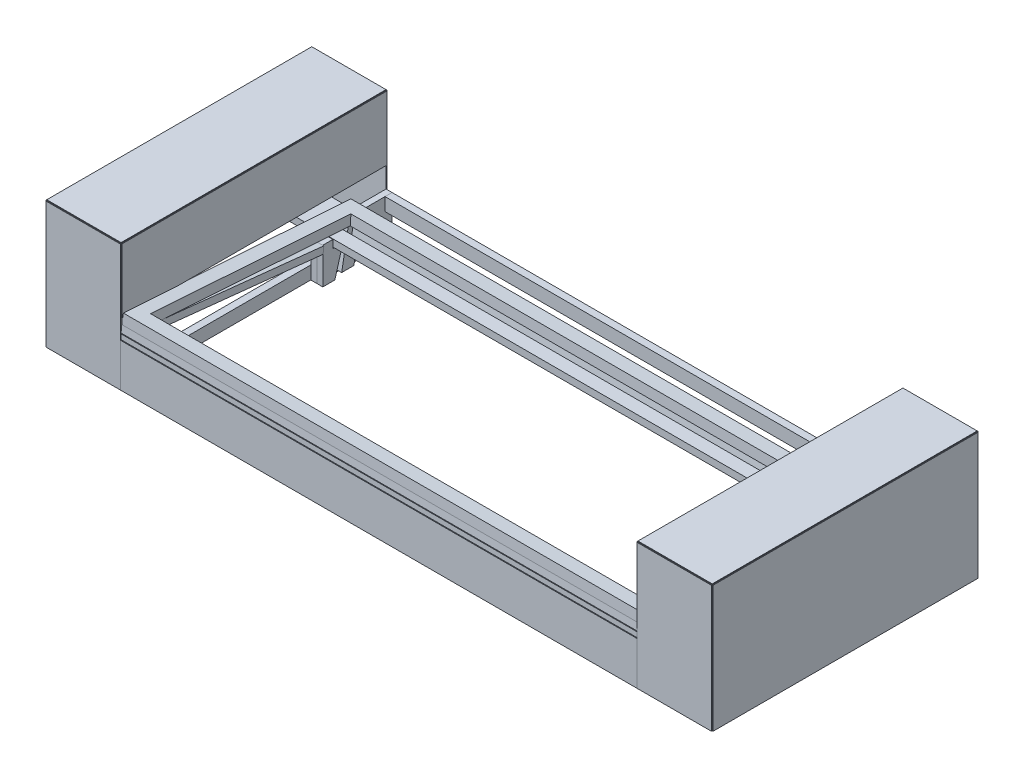
SolidWorks part; units mm, degrees
material "Balsa"
ref_plane "Front Plane" through (0, 0, 0) normal (0, 0, 1) x (1, 0, 0)
ref_plane "Top Plane" through (0, 0, 0) normal (0, 1, 0) x (1, 0, 0)
ref_plane "Right Plane" through (0, 0, 0) normal (1, 0, 0) x (0, 0, -1)
sketch "Sketch1" plane through (0, 0, 0) normal (0, 0, 1) x (1, 0, 0)
  line L0 (0, 0) -> (0, 288750.7845) construction
  line L1 (-817.5625, 0) -> (-1052.5125, 0) construction
  line L2 (-817.5625, 0) -> (-817.5625, 400.05) construction
  line L3 (-817.5625, 400.05) -> (-1052.5125, 400.05) construction
  line L4 (-1052.5125, 0) -> (-1052.5125, 400.05) construction
  line L5 (-1030.2875, 358.775) -> (-1030.2875, 219.075) construction
  line L6 (-1052.5125, 400.05) -> (-1030.2875, 400.05)
  line L7 (-1052.5125, 400.05) -> (-1052.5125, 358.775)
  line L8 (-1052.5125, 358.775) -> (-1030.2875, 358.775)
  line L9 (-1030.2875, 400.05) -> (-1030.2875, 358.775)
  line L10 (-955.675, 400.05) -> (-914.4, 400.05)
  line L11 (-955.675, 400.05) -> (-955.675, 377.825)
  line L12 (-955.675, 377.825) -> (-914.4, 377.825)
  line L13 (-914.4, 400.05) -> (-914.4, 377.825)
  line L14 (-817.5625, 400.05) -> (-839.7875, 400.05)
  line L15 (-817.5625, 400.05) -> (-817.5625, 358.775)
  line L16 (-817.5625, 358.775) -> (-839.7875, 358.775)
  line L17 (-839.7875, 400.05) -> (-839.7875, 358.775)
  line L18 (-1052.5125, 196.85) -> (-1030.2875, 196.85)
  line L19 (-1052.5125, 196.85) -> (-1052.5125, 219.075)
  line L20 (-1052.5125, 219.075) -> (-1030.2875, 219.075)
  line L21 (-1030.2875, 196.85) -> (-1030.2875, 219.075)
  line L22 (-817.5625, 196.85) -> (-839.7875, 196.85)
  line L23 (-817.5625, 196.85) -> (-817.5625, 219.075)
  line L24 (-817.5625, 219.075) -> (-839.7875, 219.075)
  line L25 (-839.7875, 196.85) -> (-839.7875, 219.075)
  line L26 (-1052.5125, 0) -> (-1030.2875, 0)
  line L27 (-1052.5125, 0) -> (-1052.5125, 41.275)
  line L28 (-1052.5125, 41.275) -> (-1030.2875, 41.275)
  line L29 (-1030.2875, 0) -> (-1030.2875, 41.275)
  line L30 (-817.5625, 0) -> (-839.7875, 0)
  line L31 (-817.5625, 0) -> (-817.5625, 41.275)
  line L32 (-817.5625, 41.275) -> (-839.7875, 41.275)
  line L33 (-839.7875, 0) -> (-839.7875, 41.275)
  line L34 (-1030.2875, 196.85) -> (-1030.2875, 41.275) construction
  line L35 (-839.7875, 41.275) -> (-839.7875, 196.85) construction
  line L36 (-839.7875, 219.075) -> (-839.7875, 358.775) construction
  line L37 (-1052.5125, 0) -> (-1052.5125, 400.05)
  line L38 (-839.7875, 0) -> (-1030.2875, 0)
  line L39 (-839.7875, 0) -> (-839.7875, 22.225)
  line L40 (-839.7875, 22.225) -> (-1030.2875, 22.225)
  line L41 (-1030.2875, 0) -> (-1030.2875, 22.225)
  line L42 (-817.5625, 400.05) -> (-1052.5125, 400.05)
  line L43 (-817.5625, 400.05) -> (-817.5625, 196.85)
  point P34 (-935.0375, 400.05)
  dimension "D1" = 22.225
  dimension "D2" = 41.275
  dimension "D3" = 190.5
  dimension "D4" = 400.05
  dimension "D5" = 196.85
  dimension "D6" = 1679.575
  dimension "D7" = 22.225
extrude "Boss-Extrude1" add sketch "Sketch1" along normal blind 838.2 contours L9 L6 L7 L8 | L13 L10 L11 L12 | L14 L17 L16 L15 | L25 L22 L23 L24 | L33 L30 L31 L32 | L26 L29 L28 L27 | L18 L21 L20 L19 region at (-828.675, 207.9625, 0) region at (-828.675, 379.4125, 0) region at (-935.0375, 388.9375, 0) region at (-1041.4, 20.6375, 0) region at (-1041.4, 207.9625, 0) region at (-1041.4, 379.4125, 0) region at (-828.675, 20.6375, 0)
extrude "Extrude-Thin1" add sketch "Sketch1<3>" along normal up to surface (838.2 mm away) separate body thin contours L42 up to face at (-1041.4, 379.4125, 838.2) thin type one direction wall 2.54
sketch "Sketch1<3>" plane through (0, 0, 0) normal (0, 0, 1) x (1, 0, 0) same geometry as "Sketch1"
extrude "Extrude-Thin2" add sketch "Sketch1<4>" along normal up to surface (838.2 mm away) separate body thin contours L37 up to face at (-1041.4, 379.4125, 838.2) thin type one direction reverse wall 2.54
sketch "Sketch1<4>" plane through (0, 0, 0) normal (0, 0, 1) x (1, 0, 0) same geometry as "Sketch1"
extrude "Extrude-Thin3" add sketch "Sketch1<5>" along normal blind 838.2 separate body thin contours L43 thin type one direction reverse wall 2.54
sketch "Sketch1<5>" plane through (0, 0, 0) normal (0, 0, 1) x (1, 0, 0) same geometry as "Sketch1"
sketch "Sketch2" plane through (-817.5625, 0, 0) normal (-1, 0, 0) x (0, 0, 1)
  line L0 (0, 219.075) -> (139.7, 219.075)
  line L1 (838.2, 219.075) -> (0, 219.075) construction
  line L2 (139.7, 219.075) -> (95.25, 358.775)
  line L3 (838.2, 358.775) -> (0, 358.775) construction
  line L4 (95.25, 358.775) -> (0, 358.775)
  line L5 (0, 358.775) -> (0, 219.075)
  dimension "D1" = 95.25
  dimension "D2" = 139.7
extrude "Boss-Extrude2" add sketch "Sketch2" along normal up to surface (22.225 mm away) separate body up to face at (-839.7875, 207.9625, 419.1)
sketch "Sketch3" plane through (0, 400.05, 0) normal (0, -1, 0) x (1, 0, 0)
  line L0 (-839.7875, 838.2) -> (-839.7875, 0) construction
  line L1 (-839.7875, 241.3) -> (-914.4, 241.3)
  line L2 (-839.7875, 241.3) -> (-839.7875, 282.575)
  line L3 (-839.7875, 282.575) -> (-914.4, 282.575)
  line L4 (-914.4, 241.3) -> (-914.4, 282.575)
  line L5 (-914.4, 838.2) -> (-914.4, 0) construction
  line L6 (-955.675, 838.2) -> (-955.675, 0) construction
  line L7 (-955.675, 241.3) -> (-1030.2875, 241.3)
  line L8 (-955.675, 241.3) -> (-955.675, 282.575)
  line L9 (-955.675, 282.575) -> (-1030.2875, 282.575)
  line L10 (-1030.2875, 241.3) -> (-1030.2875, 282.575)
  line L11 (-817.5625, 0) -> (-1052.5125, 0) construction
  line L12 (-839.7875, 584.2) -> (-914.4, 584.2)
  line L13 (-839.7875, 584.2) -> (-839.7875, 625.475)
  line L14 (-839.7875, 625.475) -> (-914.4, 625.475)
  line L15 (-914.4, 584.2) -> (-914.4, 625.475)
  line L16 (-955.675, 584.2) -> (-1030.2875, 584.2)
  line L17 (-955.675, 584.2) -> (-955.675, 625.475)
  line L18 (-955.675, 625.475) -> (-1030.2875, 625.475)
  line L19 (-1030.2875, 584.2) -> (-1030.2875, 625.475)
  line L20 (-1030.2875, 838.2) -> (-1030.2875, 0) construction
  point P24 (-1030.2875, 263.525)
  point P27 (-1030.2875, 584.2)
  dimension "D1" = 241.3
  dimension "D2" = 584.2
  dimension "D3" = 41.275
extrude "Boss-Extrude3" add sketch "Sketch3" along normal up to surface (22.225 mm away) separate body up to face at (-935.0375, 377.825, 419.1)
sketch "Sketch4" plane through (0, 0, 0) normal (0, -1, 0) x (1, 0, 0)
  line L0 (-839.7875, 838.2) -> (-839.7875, 0) construction
  line L1 (-1030.2875, 838.2) -> (-839.7875, 838.2)
  line L2 (-1030.2875, 838.2) -> (-1030.2875, 727.075)
  line L3 (-1030.2875, 727.075) -> (-839.7875, 727.075)
  line L4 (-839.7875, 838.2) -> (-839.7875, 727.075)
  line L5 (-1030.2875, 838.2) -> (-1030.2875, 0) construction
  line L6 (-839.7875, 0) -> (-1030.2875, 0)
  line L7 (-839.7875, 0) -> (-839.7875, 111.125)
  line L8 (-839.7875, 111.125) -> (-1030.2875, 111.125)
  line L9 (-1030.2875, 0) -> (-1030.2875, 111.125)
  line L10 (-817.5625, 838.2) -> (-1052.5125, 838.2)
  line L11 (-817.5625, 0) -> (-1052.5125, 0)
  line M3 (-1030.2875, 0) -> (-1030.2875, 838.2)
  dimension "D1" = 111.125
extrude "Boss-Extrude4" add sketch "Sketch4" against normal blind 22.225 separate body contours L7 L8 L6 M3 | L4 L1 L3 M3 region at (-935.0375, 0, 55.5625) region at (-935.0375, 0, 782.6375)
extrude "Extrude-Thin4" add sketch "Sketch4<3>" against normal up to surface (400.05 mm away) separate body thin contours L10 up to face at (-935.0375, 400.05, 419.1) thin type one direction wall 2.54
sketch "Sketch4<3>" plane through (0, 0, 0) normal (0, -1, 0) x (1, 0, 0) same geometry as "Sketch4"
extrude "Extrude-Thin5" add sketch "Sketch4<4>" against normal up to surface (400.05 mm away) separate body thin contours L11 up to face at (-935.0375, 400.05, 419.1) thin type one direction reverse wall 2.54
sketch "Sketch4<4>" plane through (0, 0, 0) normal (0, -1, 0) x (1, 0, 0) same geometry as "Sketch4"
mirror "Mirror Arm Geo" about plane through (0, 0, 0) normal (1, 0, 0) of bodies 115 134 103 107 114 104 137 108 135 109 113 111 105 101 133 102 106 110 112
sketch "Sketch5" plane through (-817.5625, 0, 0) normal (1, 0, 0) x (0, 0, -1)
  line L0 (-79.375, 126.2347) -> (-86.6927, 85.6136)
  line L1 (0, 0) -> (-238.125, 0)
  line L2 (0, 0) -> (0, 130.175)
  line L3 (0, 130.175) -> (-238.125, 130.175)
  line L4 (-238.125, 0) -> (-238.125, 130.175)
  line L5 (0, 22.225) -> (-41.275, 22.225)
  line L6 (0, 22.225) -> (0, 0)
  line L7 (0, 0) -> (-41.275, 0)
  line L8 (-41.275, 22.225) -> (-41.275, 0)
  line L9 (0, 130.175) -> (-22.225, 130.175)
  line L10 (0, 130.175) -> (0, 88.9)
  line L11 (0, 88.9) -> (-22.225, 88.9)
  line L12 (-22.225, 130.175) -> (-22.225, 88.9)
  line L13 (-204.8172, 92.075) -> (-163.5422, 92.075)
  line L14 (-204.8172, 92.075) -> (-204.8172, 114.3)
  line L15 (-204.8172, 114.3) -> (-163.5422, 114.3)
  line L16 (-163.5422, 92.075) -> (-163.5422, 114.3)
  line L17 (-79.375, 126.2347) -> (-101.2479, 130.175)
  line L18 (-86.6927, 85.6136) -> (-108.5656, 89.5539)
  line L19 (-101.2479, 130.175) -> (-108.5656, 89.5539)
  line L20 (-139.7, 9.525) -> (-178.4133, 9.525)
  line L21 (-178.4133, 9.525) -> (-156.6787, 130.175)
  line L22 (-156.6787, 130.175) -> (-119.1823, 123.4202)
  line L23 (-119.1823, 123.4202) -> (-139.7, 9.525)
  line L24 (-119.1823, 123.4202) -> (-126.5, 82.799)
  line L25 (-126.5, 82.799) -> (-148.3729, 86.7394)
  line L26 (-148.3729, 86.7394) -> (-141.0552, 127.3605)
  line L27 (-141.0552, 127.3605) -> (-119.1823, 123.4202)
  line L28 (-200.025, 0) -> (-174.625, 88.9)
  line L29 (-174.625, 88.9) -> (-206.375, 88.9)
  line L30 (-206.375, 88.9) -> (-206.375, 114.3)
  line L31 (-206.375, 114.3) -> (-238.125, 114.3)
  line L32 (-838.2, 0) -> (-838.2, 136.525)
  line L33 (-838.2, 0) -> (-815.975, 0)
  line L34 (-838.2, 0) -> (-838.2, 41.275)
  line L35 (-838.2, 41.275) -> (-815.975, 41.275)
  line L36 (-815.975, 0) -> (-815.975, 41.275)
  line L37 (-838.2, 400.05) -> (-838.2, 196.85) construction
  line L38 (-838.2, 196.85) -> (-838.2, 219.075) construction
  line L39 (-838.2, 154.7249) -> (-240.4372, 92.1956)
  line L40 (-815.975, 111.125) -> (-838.2, 111.125)
  line L41 (-815.975, 111.125) -> (-815.975, 152.4)
  line L42 (-815.975, 152.4) -> (-838.2, 152.4)
  line L43 (-838.2, 111.125) -> (-838.2, 152.4)
  line L44 (-838.2, 154.7249) -> (-835.8878, 176.8292)
  line L45 (-240.4372, 92.1956) -> (-238.125, 114.3)
  line L46 (-835.8878, 176.8292) -> (-238.125, 114.3)
  line L47 (-838.2, 400.05) -> (-838.2, 0) construction
  line L48 (-838.2, 0) -> (0, 0) construction
  line L49 (-815.975, 12.7) -> (-793.75, 12.7)
  line L50 (-815.975, 12.7) -> (-815.975, 150.0751)
  line L51 (-815.975, 150.0751) -> (-793.75, 150.0751)
  line L52 (-793.75, 12.7) -> (-793.75, 150.0751)
  line L53 (-835.8878, 176.8292) -> (-113.3916, 127.2017)
  line L54 (-835.8878, 176.8292) -> (-833.7069, 208.5792)
  line L55 (-113.3916, 127.2017) -> (-111.2108, 158.9517)
  line L56 (-833.7069, 208.5792) -> (-111.2108, 158.9517)
  line L57 (-838.2, 154.7249) -> (-797.149, 150.4307)
  line L58 (-838.2, 154.7249) -> (-835.8878, 176.8292)
  line L59 (-797.149, 150.4307) -> (-794.8367, 172.5351)
  line L60 (-835.8878, 176.8292) -> (-794.8367, 172.5351)
  point P53 (-777.9262, 170.7662)
  point P58 (-772.919, 147.8961)
  line M26 (0, 0) -> (0, 41.275)
  line M27 (0, 41.275) -> (-838.2, 41.275)
  line M28 (-838.2, 41.275) -> (-838.2, 0)
  line M29 (-838.2, 0) -> (0, 0)
  dimension "D1" = 238.125
  dimension "D2" = 130.175
  dimension "D3" = 22.225
  dimension "D4" = 16.4526
  dimension "D5" = 139.7
  dimension "D6" = 88.9
  dimension "D7" = 31.75
  dimension "D8" = 38.1
  dimension "D9" = 41.275
  dimension "D10" = 57.15
  dimension "D11" = 9.525
  dimension "D12" = 31.75
  dimension "D13" = 38.1
  dimension "D14" = 3.175
  dimension "D15" = 136.525
  dimension "D16" = 152.4
  dimension "D17" = 12.7
  dimension "D18" = 31.75
  dimension "D19" = 41.275
extrude "Boss-Extrude6" add sketch "Sketch5" along normal blind 19.05 separate body contours L28 L4 M29 M27 | L30 L31 L4 L28 L29 M27 | L28 L1 L8 L5 L2 L23 L20 L21 M27 | L23 L21 L20 M27 | L25 L26 L22 L21 L23 M27 | L31 L30 L29 L28 L21 L13 L14 L15 L16 L3 L4 M27 | L13 L16 L15 L14 | L17 L19 L18 L0 | L26 L25 L23 L22 | L22 L23 L2 L11 L12 L3 L17 L0 L18 L19 M27 | L3 L12 L11 L2 | L5 L8 L1 M26 region at (-817.5625, 80.4208, 65.622) region at (-817.5625, 107.8943, 93.9703) region at (-817.5625, 109.5375, 11.1125) region at (-817.5625, 103.1875, 184.1797) region at (-817.5625, 111.3388, 161.297) region at (-817.5625, 76.002, 150.5246) region at (-817.5625, 105.0798, 133.7776) region at (-817.5625, 20.8437, 96.6664) region at (-817.5625, 74.2181, 212.5406) region at (-817.5625, 25.4, 156.1968) region at (-817.5625, 11.1125, 20.6375) region at (-817.5625, 21.5595, 215.9951)
extrude "Boss-Extrude7" add sketch "Sketch5<3>" along normal blind 19.05 from surface separate body contours L28 L4 M29 M27 | L30 L31 L4 L28 L29 M27 | L25 L26 L22 L21 L23 M27 | L26 L25 L23 L22 | L23 L21 L20 M27 region at (-817.5625, 76.002, 150.5246) region at (-817.5625, 105.0798, 133.7776) region at (-817.5625, 74.2181, 212.5406) region at (-817.5625, 25.4, 156.1968) region at (-817.5625, 21.5595, 215.9951) starting at face at (-798.5125, 92.5574, 122.7868)
sketch "Sketch5<3>" plane through (-817.5625, 0, 0) normal (1, 0, 0) x (0, 0, -1) same geometry as "Sketch5"
extrude "Boss-Extrude9" add sketch "Sketch5<4>" along normal offset from surface (1597.025 mm away) 19.05 from surface separate body contours L5 L8 L1 M26 | L3 L12 L11 L2 | L17 L19 L18 L0 | L13 L16 L15 L14 region at (-817.5625, 103.1875, 184.1797) region at (-817.5625, 107.8943, 93.9703) region at (-817.5625, 109.5375, 11.1125) region at (-817.5625, 11.1125, 20.6375) up to face at (817.5625, 20.6375, 419.1) starting at face at (-798.5125, 92.5574, 122.7868)
sketch "Sketch5<4>" plane through (-817.5625, 0, 0) normal (1, 0, 0) x (0, 0, -1) same geometry as "Sketch5"
extrude "Boss-Extrude10" add sketch "Sketch5<5>" along normal offset from surface (1558.925 mm away) 19.05 from surface separate body contours L26 L25 L23 L22 region at (-817.5625, 105.0798, 133.7776) up to face at (798.5125, 107.8943, 93.9703) starting at face at (-779.4625, 68.1613, 148.4936)
sketch "Sketch5<5>" plane through (-817.5625, 0, 0) normal (1, 0, 0) x (0, 0, -1) same geometry as "Sketch5"
extrude "Boss-Extrude11" add sketch "Sketch5<7>" along normal up to surface (1635.125 mm away) separate body contours L36 M29 M27 M28 | L43 L32 L40 L41 L42 | L39 L59 L46 L44 region at (-817.5625, 163.63, 816.5184) region at (-817.5625, 131.7625, 827.0875) region at (-817.5625, 20.6375, 827.0875) up to face at (817.5625, 20.6375, 419.1)
sketch "Sketch5<7>" plane through (-817.5625, 0, 0) normal (1, 0, 0) x (0, 0, -1) same geometry as "Sketch5"
extrude "Boss-Extrude13" add sketch "Sketch5<8>" along normal blind 41.275 separate body contours L52 L51 L41 L50 M27 | L49 L52 L36 M27 region at (-817.5625, 95.6751, 804.8625) region at (-817.5625, 26.9875, 804.8625)
sketch "Sketch5<8>" plane through (-817.5625, 0, 0) normal (1, 0, 0) x (0, 0, -1) same geometry as "Sketch5"
extrude "Extrude-Thin6" add sketch "Sketch5<9>" along normal up to surface (1635.125 mm away) separate body thin contours L32 up to face at (817.5625, 200.025, 839.47) thin type one direction reverse wall 2.54
sketch "Sketch5<9>" plane through (-817.5625, 0, 0) normal (1, 0, 0) x (0, 0, -1) same geometry as "Sketch5"
extrude "Boss-Extrude14" add sketch "Sketch5<10>" along normal blind 41.275 separate body contours L46 L44 L39 L45 region at (-817.5625, 132.3653, 517.637)
sketch "Sketch5<10>" plane through (-817.5625, 0, 0) normal (1, 0, 0) x (0, 0, -1) same geometry as "Sketch5"
extrude "Boss-Extrude15" add sketch "Sketch5<11>" along normal blind 44.45 separate body contours L54 L56 L55 L53
sketch "Sketch5<11>" plane through (-817.5625, 0, 0) normal (1, 0, 0) x (0, 0, -1) same geometry as "Sketch5"
mirror "Mirror2" about plane through (0, 0, 0) normal (1, 0, 0) of bodies 145 142 144 160 164 166
sketch "Sketch7" plane through (0, 150.6021, -10.3447) normal (0, 0.9976, -0.0685) x (1, 0, 0)
  line L0 (-773.1125, -846.0405) -> (-773.1125, -121.8419) construction
  line L1 (-773.1125, -846.0405) -> (773.1125, -846.0405)
  line L2 (-773.1125, -846.0405) -> (-773.1125, -801.5905)
  line L3 (-773.1125, -801.5905) -> (773.1125, -801.5905)
  line L4 (773.1125, -846.0405) -> (773.1125, -801.5905)
  line L5 (773.1125, -121.8419) -> (-773.1125, -121.8419)
  line L6 (773.1125, -121.8419) -> (773.1125, -166.2919)
  line L7 (773.1125, -166.2919) -> (-773.1125, -166.2919)
  line L8 (-773.1125, -121.8419) -> (-773.1125, -166.2919)
  line L9 (773.1125, -846.0405) -> (773.1125, -121.8419) construction
  point P12 (773.1125, -715.6261)
  dimension "D1" = 44.45
extrude "Boss-Extrude16" add sketch "Sketch7" against normal up to surface (31.8248 mm away) up to face at (795.3375, 152.0155, 474.6397)
equation "\"D7@Sketch1\"=\"D1@Sketch1\""
